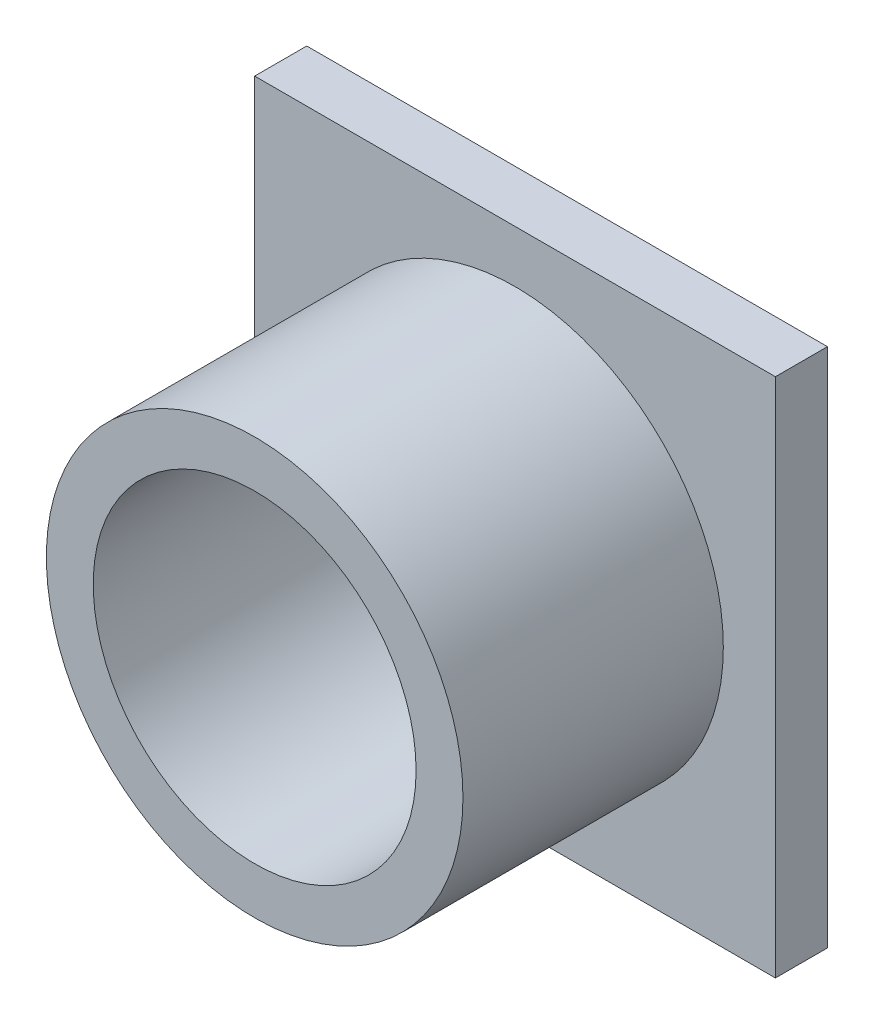
SolidWorks part; units mm, degrees
ref_plane "Front Plane" through (0, 0, 0) normal (0, 0, 1) x (1, 0, 0)
ref_plane "Top Plane" through (0, 0, 0) normal (0, 1, 0) x (1, 0, 0)
ref_plane "Right Plane" through (0, 0, 0) normal (1, 0, 0) x (0, 0, -1)
sketch "Sketch3" plane through (0, 0, 0) normal (0, 0, 1) x (1, 0, 0)
  line L1 (-5, -5) -> (5, -5)
  line L2 (-5, -5) -> (-5, 5)
  line L3 (-5, 5) -> (5, 5)
  line L4 (5, -5) -> (5, 5)
  line L5 (-5, -5) -> (5, 5) construction
  line L6 (-5, 5) -> (5, -5) construction
  point P0 (0, 0)
  dimension "D1" = 10
  dimension "D2" = 10
extrude "Boss-Extrude1" add sketch "Sketch3" along normal blind 1 contours L3 L4 L1 L2
sketch "Sketch4" plane through (0, 0, 1) normal (0, 0, 1) x (1, 0, 0)
  circle A0 centre (0, 0) radius 4
extrude "Boss-Extrude2" add sketch "Sketch4" along normal blind 5
sketch "Sketch5" plane through (0, 0, 6) normal (0, 0, 1) x (1, 0, 0)
  circle A0 centre (0, 0) radius 3.1
extrude "Cut-Extrude1" cut sketch "Sketch5" against normal blind 4.5
